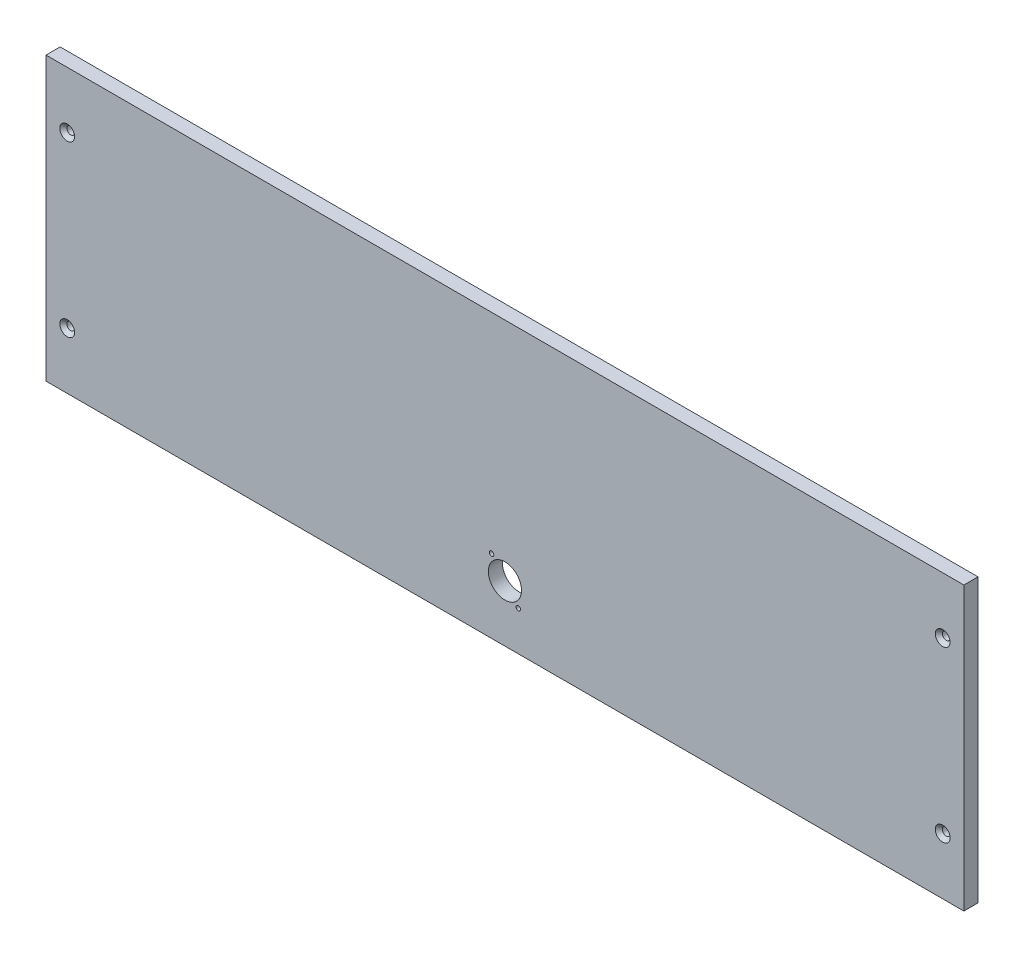
SolidWorks part; units mm, degrees
ref_plane "Plan de face" through (0, 0, 0) normal (0, 0, 1) x (1, 0, 0)
ref_plane "Plan de dessus" through (0, 0, 0) normal (0, 1, 0) x (1, 0, 0)
ref_plane "Plan de droite" through (0, 0, 0) normal (1, 0, 0) x (0, 0, -1)
sketch "Esquisse1" plane through (0, 0, 0) normal (0, 0, 1) x (1, 0, 0)
  line L1 (0, 0) -> (650, 0)
  line L2 (0, 0) -> (0, 200)
  line L3 (0, 200) -> (650, 200)
  line L4 (650, 0) -> (650, 200)
  dimension "D1" = 200
  dimension "D2" = 650
extrude "Boss.-Extru.1" add sketch "Esquisse1" along normal blind 10
sketch "Esquisse2" plane through (0, 0, 10) normal (0, 0, 1) x (1, 0, 0)
  line L0 (0, 200) -> (0, 0) construction
  line L1 (650, 200) -> (0, 200) construction
  line L2 (0, 0) -> (650, 0) construction
  line L3 (650, 0) -> (650, 200) construction
  circle A0 centre (15, 160) radius 2.75
  circle A1 centre (635, 160) radius 2.75
  circle A2 centre (15, 40) radius 2.75
  circle A3 centre (635, 40) radius 2.75
  dimension "D1" = 5.5
  dimension "D2" = 5.5
  dimension "D3" = 5.5
  dimension "D4" = 5.5
  dimension "D5" = 15
  dimension "D6" = 15
  dimension "D7" = 40
  dimension "D8" = 40
  dimension "D9" = 40
  dimension "D10" = 40
  dimension "D11" = 15
  dimension "D12" = 15
extrude "Enlèv. mat.-Extru.1" cut sketch "Esquisse2" against normal blind 10
chamfer "Chanfrein1" distance 2.5 angle 45 4 edges at (17.75, 160, 10) (17.75, 40, 10) (637.75, 40, 10) (637.75, 160, 10)
sketch "Esquisse3" plane through (0, 0, 10) normal (0, 0, 1) x (1, 0, 0)
  line L0 (0, 0) -> (650, 0) construction
  line L1 (334.5004, 28.0006) -> (325, 40)
  line L2 (325, 40) -> (315.4996, 51.9994)
  line L3 (325, 40) -> (265.8175, 40)
  line L4 (325, 40) -> (364.3682, 40)
  circle A0 centre (325, 40) radius 11.75
  circle A1 centre (315.4996, 51.9994) radius 1.6
  circle A2 centre (334.5004, 28.0006) radius 1.6
  point P4 (325, 0)
  dimension "D1" = 23.5
  dimension "D4" = 3.2
  dimension "D5" = 3.2
  dimension "D2" = 0
  dimension "D3" = 40
  dimension "D6" = 30.61
  dimension "D7" = 15.305
  dimension "D8" = 51.63
  dimension "D9" = 180
  dimension "D10" = 51.63
  dimension "D11" = 15.305
extrude "Enlèv. mat.-Extru.2" cut sketch "Esquisse3" against normal blind 10 contours L3 A0 L1 | L4 A0 L2 | L1 A0 L4 | L2 A0 L3 | A1 | A2 region at (314.1, 52.6764, 10) region at (322.2589, 34.3335, 10) region at (331.8154, 36.7031, 10) region at (335.1774, 29.4002, 10) region at (318.1846, 43.2969, 10) region at (327.7411, 45.6665, 10)
